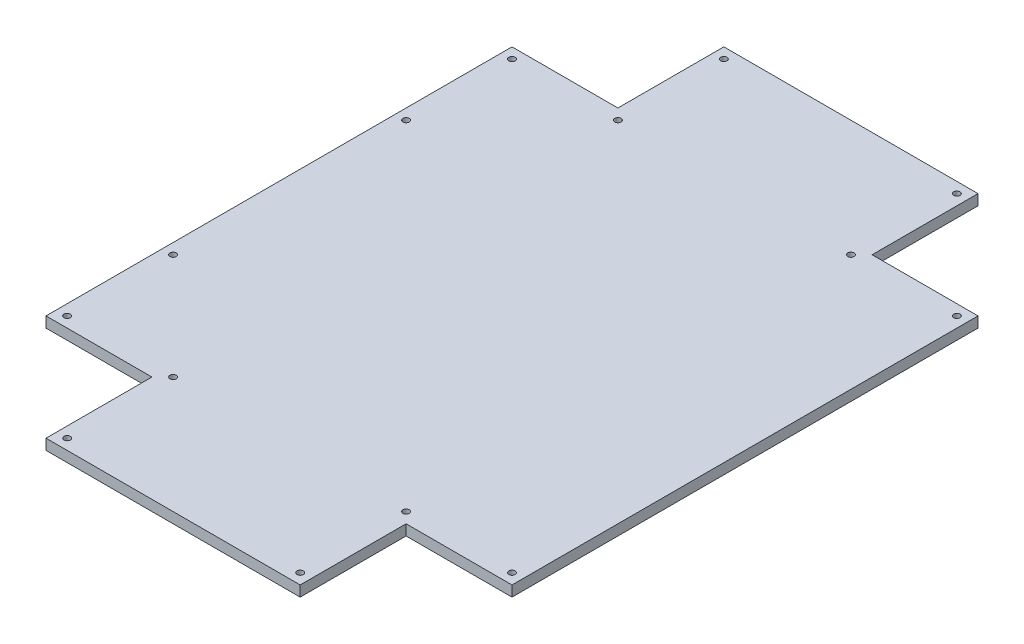
SolidWorks part; units mm, degrees
ref_plane "Plan de face" through (0, 0, 0) normal (0, 0, 1) x (1, 0, 0)
ref_plane "Plan de dessus" through (0, 0, 0) normal (0, 1, 0) x (1, 0, 0)
ref_plane "Plan de droite" through (0, 0, 0) normal (1, 0, 0) x (0, 0, -1)
sketch "Esquisse1" plane through (0, 0, 0) normal (0, 1, 0) x (1, 0, 0)
  line L0 (-60, 110) -> (-60, 160)
  line L1 (110, -110) -> (60, -110)
  line L2 (110, -110) -> (110, 110)
  line L3 (110, 110) -> (60, 110)
  line L4 (-110, -110) -> (-110, 0)
  line L5 (110, -110) -> (-110, 110) construction
  line L6 (110, 110) -> (-110, -110) construction
  line L7 (-60, 160) -> (60, 160)
  line L8 (60, 160) -> (60, 110)
  line L9 (0, 160) -> (0, -89.8749) construction
  line L10 (-110, 0) -> (110, 0) construction
  line L11 (-105, -105) -> (-105, -50) construction
  line L12 (-55, -105) -> (-55, -160) construction
  line L13 (-60, 110) -> (-110, 110)
  line L14 (60, -160) -> (60, -110)
  line L15 (-60, -160) -> (60, -160)
  line L16 (-60, -110) -> (-60, -160)
  line L17 (-60, -110) -> (-110, -110)
  line L28 (-110, 0) -> (-110, 110)
  line L33 (-105, -105) -> (105, -105) construction
  line L34 (105, -105) -> (105, 0) construction
  circle A0 centre (-105, -105) radius 1.5
  circle A1 centre (-105, -55) radius 1.5
  circle A2 centre (-55, -105) radius 1.5
  circle A5 centre (-5, -105) radius 1.5 [skipped]
  circle A6 centre (45, -105) radius 1.5 [skipped]
  circle A7 centre (-55, -155) radius 1.5
  circle A8 centre (-55, 155) radius 1.5
  circle A9 centre (-55, 105) radius 1.5
  circle A10 centre (-105, 105) radius 1.5
  circle A11 centre (-105, 55) radius 1.5
  circle A12 centre (55, -155) radius 1.5
  circle A13 centre (55, -105) radius 1.5
  circle A14 centre (105, -105) radius 1.5
  circle A15 centre (105, 105) radius 1.5
  circle A16 centre (55, 105) radius 1.5
  circle A17 centre (55, 155) radius 1.5
  point P0 (0, 0)
  point P33 (0, 0)
  dimension "D4" = 3
  dimension "D6" = 50
  dimension "D14" = 5
  dimension "D16" = 5
  dimension "D1" = 220
  dimension "D2" = 50
  dimension "D3" = 50
  dimension "D5" = 5
  dimension "D7" = 120
  dimension "D13" = 2
  dimension "D15" = 4
  dimension "D17" = 2
extrude "Boss.-Extru.1" add sketch "Esquisse1" along normal blind 5
